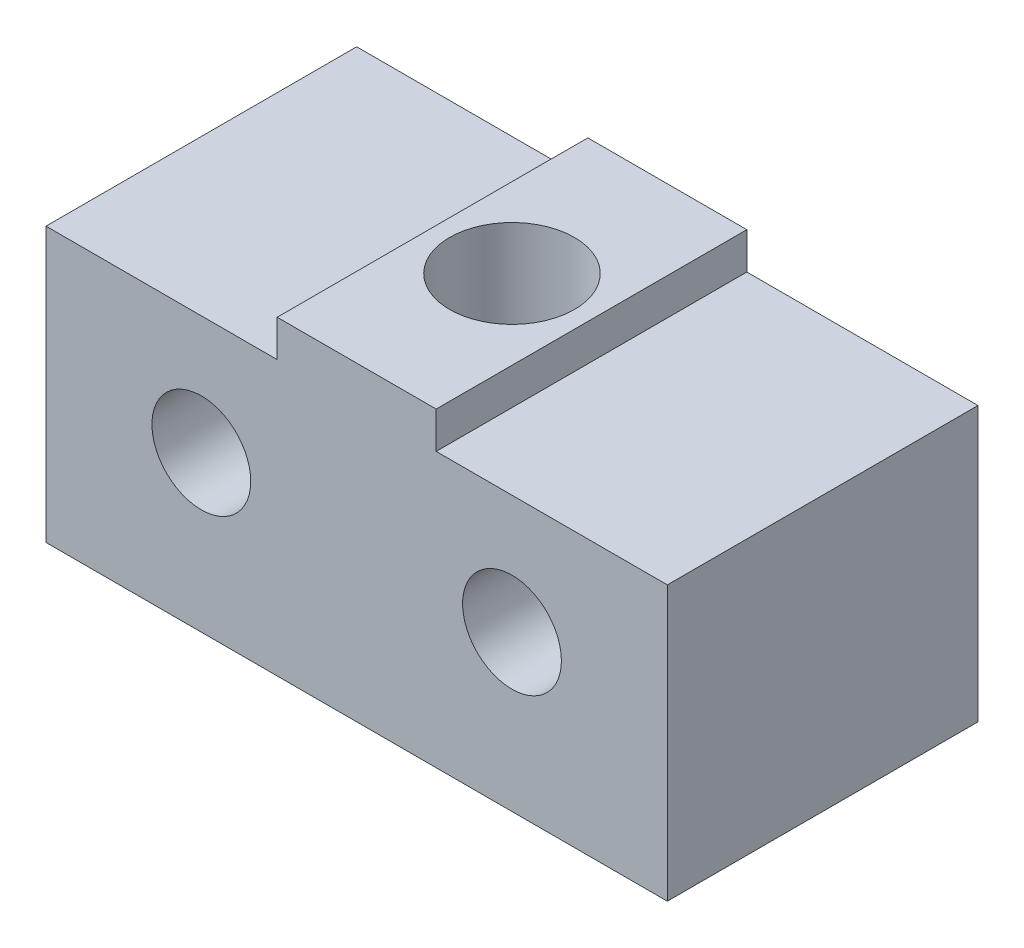
SolidWorks part; units mm, degrees
ref_plane "Front Plane" through (0, 0, 0) normal (0, 0, 1) x (1, 0, 0)
ref_plane "Top Plane" through (0, 0, 0) normal (0, 1, 0) x (1, 0, 0)
ref_plane "Right Plane" through (0, 0, 0) normal (1, 0, 0) x (0, 0, -1)
sketch "Sketch5" plane through (0, 0, 0) normal (0, 0, 1) x (1, 0, 0)
  line L1 (0, 0) -> (-25.4, 0)
  line L2 (0, 0) -> (0, -12.7)
  line L3 (0, -12.7) -> (-25.4, -12.7)
  line L4 (-25.4, 0) -> (-25.4, -12.7)
  dimension "D1" = 25.4
  dimension "D2" = 12.7
extrude "Boss-Extrude2" add sketch "Sketch5" along normal blind 12.7
sketch "Sketch6" plane through (0, 0, 12.7) normal (0, 0, 1) x (1, 0, 0)
  line L0 (-12.7, 0) -> (-12.7, -12.7) construction
  line L1 (0, 0) -> (-25.4, 0) construction
  line L2 (-25.4, -12.7) -> (0, -12.7) construction
  line L3 (-25.4, -6.35) -> (0, -6.35) construction
  line L4 (-25.4, 0) -> (-25.4, -12.7) construction
  line L5 (0, -12.7) -> (0, 0) construction
  line L7 (-25.4, 0) -> (-15.95, 0)
  line L8 (-25.4, 0) -> (-25.4, -1.5)
  line L9 (-25.4, -1.5) -> (-15.95, -1.5)
  line L10 (-15.95, 0) -> (-15.95, -1.5)
  line L11 (0, 0) -> (-9.45, 0)
  line L12 (0, 0) -> (0, -1.5)
  line L13 (0, -1.5) -> (-9.45, -1.5)
  line L14 (-9.45, 0) -> (-9.45, -1.5)
  line L15 (-19.05, 0) -> (-19.05, -12.7) construction
  line L16 (-6.35, 0) -> (-6.35, -12.7) construction
  dimension "D1" = 1.5
  dimension "D2" = 1.5
  dimension "D3" = 3.25
  dimension "D4" = 3.25
  dimension "D5" = 12.7
  dimension "D6" = 6.35
  dimension "D7" = 6.35
hole_wizard "#10-32 Tapped Hole1" positions "Sketch9" profile "Sketch10" tap size "#10-32" standard "ANSI Inch" end condition through all
sketch "Sketch9" plane through (0, 0, 12.7) normal (0, 0, 1) x (1, 0, 0)
  line L0 (-19.05, 0) -> (-19.05, -12.7) construction
  line L1 (-25.4, -6.35) -> (0, -6.35) construction
  point P0 (-19.05, -6.35)
sketch "Sketch10" plane through (-19.05, -6.35, 12.7) normal (1, 0, 0) x (0, -1, 0)
  line L0 (0, 0) -> (0, 12.7)
  line L1 (0, 12.7) -> (2.0193, 12.7)
  line L2 (2.0193, 12.7) -> (2.0193, 0)
  line L5 (2.0193, 0) -> (0, 0)
  line L11 (0, -6.35) -> (0, 107.95) construction
  dimension "Thread Major Dia." = 4.0386
  dimension "Thru Tap Drill Depth" = 12.7
ref_plane "Plane1" through (-12.7, 0, 0) normal (-1, 0, 0) x (0, 0, 1)
mirror "Mirror1" about plane through (-12.7, 0, 0) normal (-1, 0, 0) of "#10-32 Tapped Hole1"
extrude "Cut-Extrude1" cut sketch "Sketch6" against normal up to surface (12.7 mm away) up to face at (-4.3307, -6.35, 0)
sketch "Sketch11" plane through (0, 0, 0) normal (0, 1, 0) x (1, 0, 0)
  line L0 (-15.95, -6.35) -> (-9.45, -6.35) construction
  line L1 (-15.95, 0) -> (-15.95, -12.7) construction
  line L2 (-9.45, 0) -> (-9.45, -12.7) construction
  line L3 (-12.7, 0) -> (-12.7, -12.7) construction
  line L4 (-9.45, 0) -> (-15.95, 0) construction
  line L5 (-9.45, -12.7) -> (-15.95, -12.7) construction
  circle A0 centre (-12.7, -6.35) radius 2.5
hole_wizard "CBORE for #10 Socket Head Cap Screw1" positions "Sketch15" profile "Sketch16" counterbore size "#10" standard "ANSI Inch" end condition through all
sketch "Sketch15" plane through (0, -12.7, 0) normal (0, -1, 0) x (-1, 0, 0)
  line L0 (15.95, -6.35) -> (9.45, -6.35) construction
  line L1 (12.7, 0) -> (12.7, -12.7) construction
  point P0 (12.7, -6.35)
sketch "Sketch16" plane through (-12.7, -12.7, 6.35) normal (1, 0, 0) x (0, 0, -1)
  line L0 (0, 0) -> (0, 12.7)
  line L1 (0, 12.7) -> (2.5527, 12.7)
  line L3 (2.5527, 12.7) -> (2.5527, 4.826)
  line L4 (2.5527, 4.826) -> (4.7625, 4.826)
  line L5 (4.7625, 4.826) -> (4.7625, 0)
  line L7 (4.7625, 0) -> (0, 0)
  line L11 (0, -6.35) -> (0, 107.95) construction
  dimension "Thru Hole Dia." = 5.1054
  dimension "Thru Hole Depth" = 12.7
  dimension "C'Bore Dia." = 9.525
  dimension "C'Bore Depth" = 4.826
